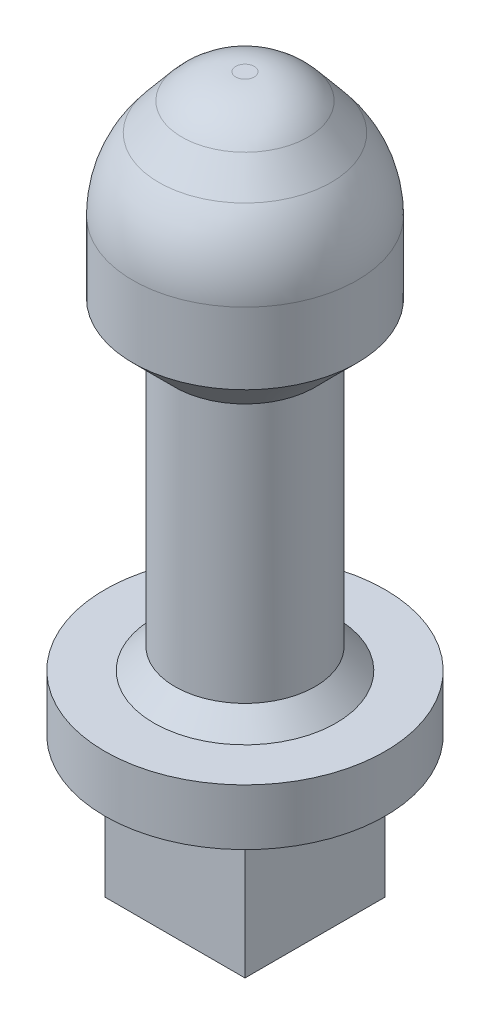
SolidWorks part; units mm, degrees
ref_plane "Front" through (0, 0, 0) normal (0, 0, 1) x (1, 0, 0)
ref_plane "Top" through (0, 0, 0) normal (0, 1, 0) x (1, 0, 0)
ref_plane "Right" through (0, 0, 0) normal (1, 0, 0) x (0, 0, -1)
sketch "Sketch1" plane through (0, 0, 0) normal (0, 1, 0) x (1, 0, 0)
  line L1 (-5, -5) -> (5, -5)
  line L2 (-5, -5) -> (-5, 5)
  line L3 (-5, 5) -> (5, 5)
  line L4 (5, -5) -> (5, 5)
  line L5 (-5, -5) -> (5, 5) construction
  line L6 (-5, 5) -> (5, -5) construction
  point P0 (0, 0)
  dimension "D1" = 10
extrude "Boss-Extrude1" add sketch "Sketch1" along normal blind 10
sketch "Sketch2" plane through (0, 10, 0) normal (0, 1, 0) x (1, 0, 0)
  circle A0 centre (0, 0) radius 10
  dimension "D1" = 20
extrude "Boss-Extrude2" add sketch "Sketch2" along normal blind 4
sketch "Sketch3" plane through (0, 14, 0) normal (0, 1, 0) x (1, 0, 0)
  circle A0 centre (0, 0) radius 5
  dimension "D1" = 10
extrude "Boss-Extrude3" add sketch "Sketch3" along normal blind 23
sketch "Sketch4" plane through (0, 0, 0) normal (0, 0, 1) x (1, 0, 0)
  line L0 (0, 37) -> (0, 51)
  line L1 (5, 37) -> (-5, 37) construction
  line L2 (0, 51) -> (0.6581, 51)
  line L3 (0, 37) -> (8, 37)
  line L4 (8, 37) -> (8, 42.1036)
  line L5 (4.4992, 49.2009) -> (6.1458, 47.2251)
  arc A0 (6.1458, 47.2251) -> (8, 42.1036) centre (0, 42.1036) cw
  arc A1 (4.4992, 49.2009) -> (0.6581, 51) centre (0.6581, 46) ccw
  point P10 (8, 45)
  point P13 (3, 51)
  dimension "D3" = 3
  dimension "D5" = 8
  dimension "D6" = 5
  dimension "D1" = 8
  dimension "D2" = 14
  dimension "D4" = 8
revolve "Revolve1" add sketch "Sketch4" angle 360 about L0
chamfer "Chamfer1" distance 3 angle 45 1 edges at (0, 37, 5)
sketch "Sketch7" plane through (0, 0, 0) normal (0, -1, 0) x (1, 0, 0)
  circle A0 centre (0, 0) radius 1.6
  dimension "D1" = 3.2
extrude "Cut-Extrude2" cut sketch "Sketch7" against normal blind 6
sketch "Sketch8" plane through (0, 0, -5) normal (0, 0, -1) x (-1, 0, 0)
  line L0 (-5, 0) -> (5, 0) construction
  line L1 (-3, 9) -> (3, 9)
  line L2 (-3, 9) -> (-3, 6)
  line L3 (-3, 6) -> (3, 6)
  line L4 (3, 9) -> (3, 6)
  line L5 (-3, 9) -> (3, 6) construction
  line L6 (-3, 6) -> (3, 9) construction
  point P0 (0, 7.5)
  dimension "D1" = 3
  dimension "D2" = 6
  dimension "D3" = 6
extrude "Cut-Extrude3" cut sketch "Sketch8" against normal blind 8
sketch "Sketch9" plane through (0, 0, 0) normal (0, -1, 0) x (1, 0, 0)
  line L5 (-1.6, 0) -> (1.6, 0)
  line L6 (1.6, 0) -> (1.6, -5)
  line L7 (5, -5) -> (-5, -5) construction
  line L8 (1.6, -5) -> (-1.6, -5)
  line L9 (-1.6, -5) -> (-1.6, 0)
  circle A2 centre (0, 0) radius 1.6 construction
  circle M6 centre (0, 0) radius 1.6
  line M10 (-5, -5) -> (5, -5)
extrude "Cut-Extrude4" cut sketch "Sketch9" against normal up to next contours L9 L6 M10 M6 region at (0, 0, -3.1113)
chamfer "Chamfer2" distance 1.5 angle 45 1 edges at (0, 14, 5)
